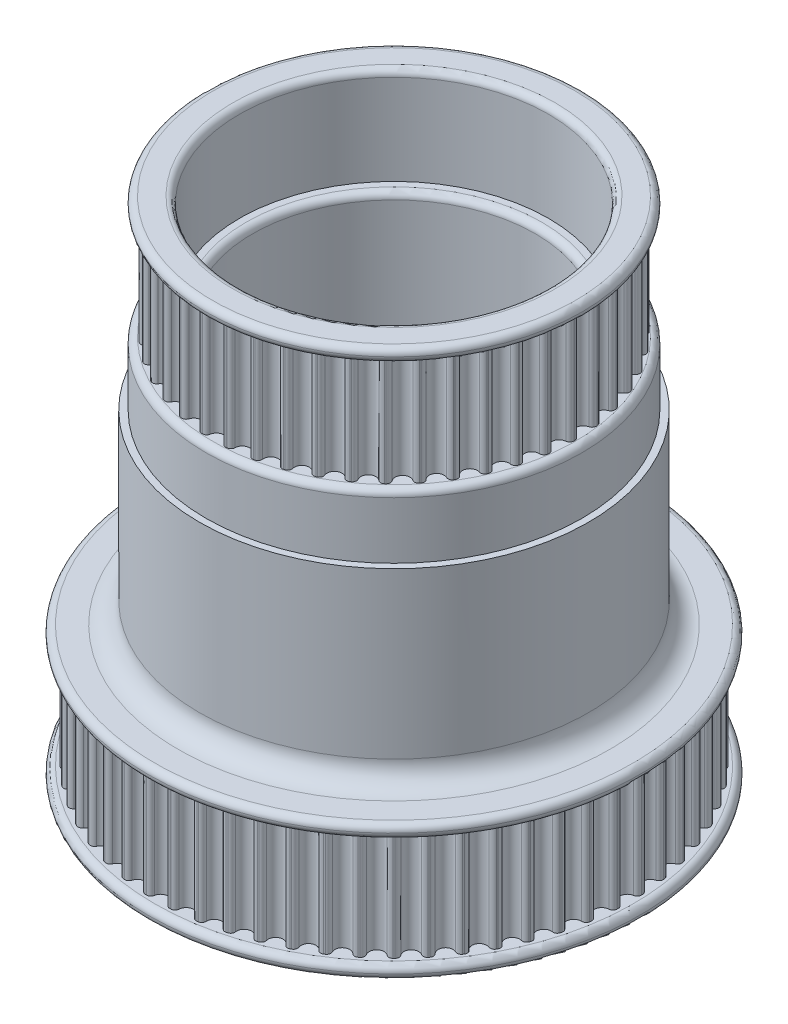
SolidWorks part; units mm, degrees
ref_plane "Front Plane" through (0, 0, 0) normal (0, 0, 1) x (1, 0, 0)
ref_plane "Top Plane" through (0, 0, 0) normal (0, 1, 0) x (1, 0, 0)
ref_plane "Right Plane" through (0, 0, 0) normal (1, 0, 0) x (0, 0, -1)
sketch "PulleyOffsets" plane through (0, 0, 0) normal (1, 0, 0) x (0, 0, -1)
  line L0 (22.225, 0) -> (-22.225, 0) construction
  line L1 (22.225, 44.45) -> (-22.225, 44.45) construction
  line L2 (0, 0) -> (0, 44.45) construction
  point P7 (0, 0)
  dimension "D1" = 44.45
ref_axis "Axis1" through (0, 34.9332, 0) along (0, -1, 0)
ref_plane "Big Pulley Plane" through (0, 0, 0) normal (0, 1, 0) x (1, 0, 0)
ref_plane "Small Pulley Plane" through (0, 44.45, 0) normal (0, 1, 0) x (1, 0, 0)
sketch "Sketch1" plane through (0, 0, 0) normal (0, 1, 0) x (1, 0, 0)
  line L0 (0, 0) -> (0, 28.2667) construction
  line L1 (0, 0) -> (2.9202, 27.7837) construction
  circle A0 centre (0, 0) radius 28.2667 construction
  circle A1 centre (0, 0) radius 27.0467 construction
  circle A2 centre (0, 27.9367) radius 0.89 construction
  circle A5 centre (2.9202, 27.7837) radius 0.89 construction
  arc A6 (0, 27.0467) -> (0.8804, 27.8061) centre (0, 27.9367) ccw
  arc A7 (0.8804, 27.8061) -> (1.3997, 28.2321) centre (1.3749, 27.7327) cw
  arc A8 (1.559, 28.2237) -> (2.031, 27.7458) centre (1.5314, 27.7245) cw
  arc A9 (2.8272, 26.8986) -> (2.031, 27.7458) centre (2.9202, 27.7837) cw
  arc A10 (1.3997, 28.2321) -> (1.559, 28.2237) centre (0, 0) cw
  arc A11 (0, 27.0467) -> (2.8272, 26.8986) centre (0, 0) ccw
  dimension "D1" = 56.5335
  dimension "D3" = 1.78
  dimension "D4" = 0.5
  dimension "D2" = 1.22
  dimension "D5" = 6
extrude "Boss-Extrude1" add sketch "Sketch1" along normal mid plane 13 contours A6 A11 A9 A8 A7 region at (0.001, 0, -0.0192)
pattern_circular "CirPattern1" count 60 over 360 about axis through (0, 34.9332, 0) along (0, -1, 0) of "Boss-Extrude1"
sketch "Sketch2" plane through (0, 0, 0) normal (1, 0, 0) x (0, 0, -1)
  line L10 (0, 6.5) -> (29.4415, 6.5) construction
  line L11 (0, 6.5) -> (0, 8.0875) construction
  line L12 (0, 8.0875) -> (29.4415, 8.0875) construction
  line L15 (29.4415, 6.5) -> (29.4415, 8.0875) construction
  line L20 (0, 34.9332) -> (0, -6.9932) construction
  line L22 (29.4415, 8.0875) -> (0, 8.0875)
  line L23 (29.4415, 8.0875) -> (29.4415, 6.5)
  line L24 (29.4415, 6.5) -> (0, 6.5)
  line L25 (0, 8.0875) -> (0, 6.5)
  dimension "D1" = 1.5875
  dimension "D2" = 29.4415
  dimension "D3" = 6.5
revolve "Revolve3" add sketch "Sketch2" angle 360 about axis through (0, 34.9332, 0) along (0, -1, 0) region at (0, 7.2937, -14.7207)
mirror "Mirror1" about plane through (0, 0, 0) normal (0, 1, 0) of "Revolve3"
sketch "Sketch6" plane through (0, 0, 0) normal (0, 1, 0) x (1, 0, 0)
  line L0 (0, 0) -> (0, 21.582) construction
  line L1 (0, 0) -> (2.8938, 21.0541) construction
  circle A0 centre (0, 0) radius 21.582 construction
  circle A1 centre (0, 0) radius 20.362 construction
  circle A2 centre (0, 21.252) radius 0.89 construction
  circle A5 centre (2.8938, 21.0541) radius 0.89 construction
  arc A6 (0, 20.362) -> (0.8793, 21.1145) centre (0, 21.252) ccw
  arc A7 (0.8793, 21.1145) -> (1.4059, 21.5362) centre (1.3733, 21.0373) cw
  arc A8 (1.5397, 21.527) -> (2.004, 21.0376) centre (1.5041, 21.0283) cw
  arc A9 (2.7726, 20.1724) -> (2.004, 21.0376) centre (2.8938, 21.0541) cw
  arc A10 (1.4059, 21.5362) -> (1.5397, 21.527) centre (0, 0) cw construction
  arc A11 (0, 20.362) -> (2.7726, 20.1724) centre (0, 0) ccw
  arc A12 (1.4059, 21.5362) -> (1.5397, 21.527) centre (0, 0) cw
  dimension "D3" = 1.78
  dimension "D4" = 0.5
  dimension "D2" = 1.22
  dimension "D1" = 43.1641
  dimension "D5" = 7.826
extrude "Boss-Extrude2" add sketch "Sketch6" along normal mid plane 13 from surface contours A6 A11 A9 A8 A7 region at (0.0017, 0, -0.025) starting at plane "Small Pulley Plane"
pattern_circular "CirPattern2" count 46 over 360 about axis through (0, 34.9332, 0) along (0, -1, 0) of "Boss-Extrude2"
sketch "Sketch9" plane through (0, 0, 0) normal (1, 0, 0) x (0, 0, -1)
  line L1 (0, 37.95) -> (22.7568, 37.95)
  line L2 (0, 37.95) -> (0, 36.3625)
  line L3 (0, 36.3625) -> (22.7568, 36.3625)
  line L4 (22.7568, 37.95) -> (22.7568, 36.3625)
  line L6 (0, 50.95) -> (22.7568, 50.95)
  line L7 (0, 50.95) -> (0, 52.5375)
  line L8 (0, 52.5375) -> (22.7568, 52.5375)
  line L9 (22.7568, 50.95) -> (22.7568, 52.5375)
  line L10 (29.4415, 8.0875) -> (29.4415, 6.5) construction
  line L11 (0, 34.9332) -> (0, -6.9932) construction
  line L12 (21.1145, 50.95) -> (20.362, 50.95) construction
  line L13 (20.1641, 37.95) -> (21.0376, 37.95) construction
  dimension "D1" = 22.7568
revolve "Revolve4" add sketch "Sketch9" angle 360 about axis through (0, 34.9332, 0) along (0, -1, 0)
sketch "Sketch10" plane through (0, -8.0875, 0) normal (0, -1, 0) x (1, 0, 0)
  circle A0 centre (0, 0) radius 18.5
  dimension "D1" = 37
extrude "Cut-Extrude1" cut sketch "Sketch10" against normal through all
sketch "Sketch11" plane through (0, 52.5375, 0) normal (0, 1, 0) x (1, 0, 0)
  circle A0 centre (0, 0) radius 22.5
  dimension "D1" = 45
extrude "Cut-Extrude2" cut sketch "Sketch11" against normal up to surface (16.175 mm away) flip side to cut up to face at (0, 36.3625, 18.5)
sketch "Sketch12" plane through (0, 0, 0) normal (0, 0, 1) x (1, 0, 0)
  line L0 (29.4415, 8.0875) -> (-29.4415, 8.0875) construction
  line L1 (18.5, 36.3625) -> (22.5, 36.3625)
  line L2 (18.5, 36.3625) -> (18.5, 8.0875) construction
  line L3 (18.5, 8.0875) -> (22.5, 8.0875)
  line L4 (22.5, 36.3625) -> (22.5, 8.0875) construction
  line L5 (22.5, 36.3625) -> (22.5, 37.95) construction
  line L6 (22.5, 30.3625) -> (22.5, 36.3625)
  line L7 (22.5, 30.3625) -> (23.2938, 30.3625)
  line L8 (22.5, 30.3625) -> (22.5, 8.0875) construction
  line L9 (22.5, 8.0875) -> (23.2938, 8.0875)
  line L10 (23.2938, 30.3625) -> (23.2938, 8.0875)
  line L11 (18.5, -8.0875) -> (18.5, 8.0875) construction
  line L12 (18.5, -1.0875) -> (16.9125, -1.0875)
  line L13 (18.5, -1.0875) -> (18.5, 40.95) construction
  line L14 (18.5, 40.95) -> (16.9125, 40.95)
  line L15 (16.9125, -1.0875) -> (16.9125, 40.95)
  line L16 (-29.4415, -8.0875) -> (29.4415, -8.0875) construction
  line L18 (18.5, -1.0875) -> (18.5, 8.0875)
  line L19 (18.5, 36.3625) -> (18.5, 40.95)
  line L20 (32.3856, 44.45) -> (-32.3856, 44.45) construction
  dimension "D1" = 6
  dimension "D2" = 0.7937
  dimension "D3" = 7
  dimension "D4" = 3.5
  dimension "D5" = 1.5875
revolve "Revolve5" add sketch "Sketch12" angle 360 about axis through (0, 34.9332, 0) along (0, -1, 0)
fillet "Fillet1" radius 2.54 1 edges at (0, 8.0875, -23.2938)
fillet "Fillet2" radius 0.7937 11 edges at (0, 40.95, 16.9125) (0, 52.5375, -18.5) (0, -8.0875, -18.5) (0, -1.0875, 16.9125) (0, -8.0875, 29.4415) (0, 8.0875, 29.4415) (0, 52.5375, 22.5) (0, 50.95, 22.5) (0, 37.95, -22.5) (0, 6.5, 29.4415) (0, -6.5, 29.4415)
equation "\"TEETH_NUM\"= 60"
equation "\"TOOTH_PITCH\"= 3mm"
equation "\"PITCH_LINE_OFFSET\"= .015in"
equation "\"DIAMETER_PER_GROOVE\"= \"OUTSIDE_DIAMETER\" / \"TEETH_NUM\" * 1in"
equation "\"PITCH_DIAMETER\"= ( ( \"TEETH_NUM\" * 3 - 1.31 ) / 3.1415 + .415 ) * 1mm"
equation "\"OUTSIDE_DIAMETER\"= \"PITCH_DIAMETER\" - \"PITCH_LINE_OFFSET\" * 2"
equation "\"D1@Sketch1\"=\"OUTSIDE_DIAMETER\""
equation "\"TOOTH_HEIGHT\"= 1.22mm"
equation "\"D2@Sketch1\"=\"TOOTH_HEIGHT\""
equation "\"TOOTH_DIAMETER\"= 1.78mm"
equation "\"INTERNAL_RADIUS\"= .5mm"
equation "\"D3@Sketch1\"=\"TOOTH_DIAMETER\""
equation "\"D5@Sketch1\"=360 / \"TEETH_NUM\""
equation "\"D4@Sketch1\"=\"INTERNAL_RADIUS\""
equation "\"D1@CirPattern1\"=\"TEETH_NUM\""
equation "\"BELT_GAP\"= 13mm"
equation "\"D2@Sketch2\"=\"PITCH_DIAMETER\"/2+1/32"
equation "\"D3@Sketch2\"=\"BELT_GAP\"/2"
equation "\"2_TEETH_NUM\"= 46"
equation "\"2_PITCH_DIAMETER\"= ( ( \"2_TEETH_NUM\" * 3 - 1.31 ) / 3.1415 + .415 ) * 1mm"
equation "\"2_OUTSIDE_DIAMETER\"= \"2_PITCH_DIAMETER\" - \"PITCH_LINE_OFFSET\" * 2"
equation "\"2_DIAMETER_PER_GROOVE\"= \"2_OUTSIDE_DIAMETER\" / \"2_TEETH_NUM\" * 1in"
equation "\"D5@Sketch6\"=360/\"2_TEETH_NUM\""
equation "\"D1@Sketch6\"=\"2_OUTSIDE_DIAMETER\""
equation "\"D2@Sketch6\"=\"TOOTH_HEIGHT\""
equation "\"D3@Sketch6\"=\"TOOTH_DIAMETER\""
equation "\"D4@Sketch6\"=\"INTERNAL_RADIUS\""
equation "\"2_BELT_GAP\"= 13mm"
equation "\"D1@CirPattern2\"=\"2_TEETH_NUM\""
equation "\"D1@Boss-Extrude2\"=\"2_BELT_GAP\""
equation "\"Pulley_OffSets\" = 1.75"
equation "\"D1@PulleyOffsets\" = \"Pulley_OffSets\""
equation "\"D1@Boss-Extrude1\"=\"BELT_GAP\""
equation "\"D1@Sketch9\"=\"2_PITCH_DIAMETER\"/2+1/32"
